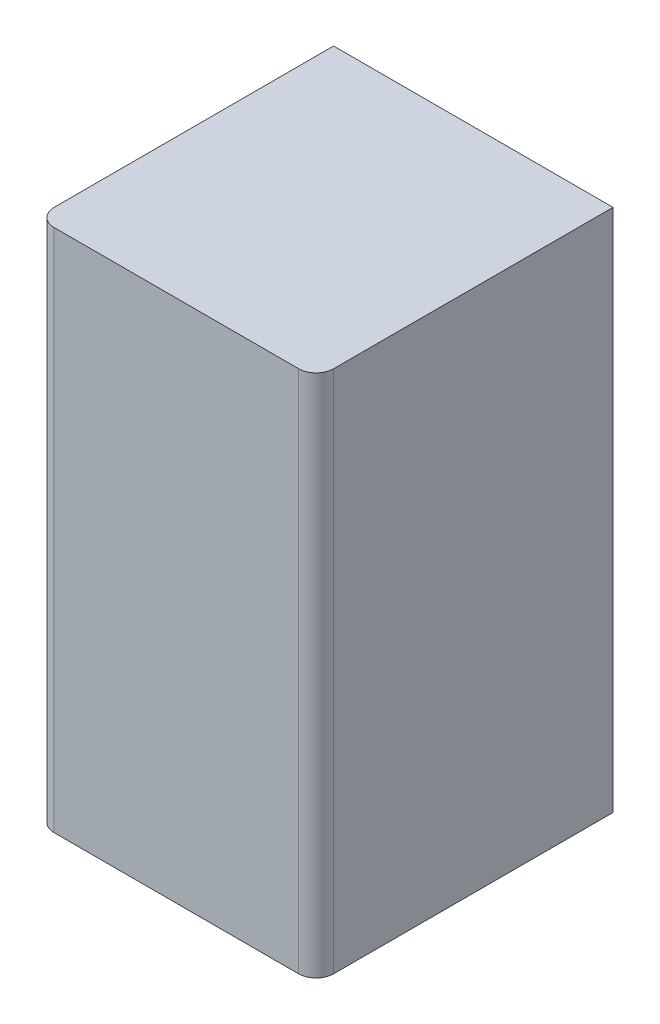
SolidWorks part; units mm, degrees
ref_plane "前视基准面" through (0, 0, 0) normal (0, 0, 1) x (1, 0, 0)
ref_plane "上视基准面" through (0, 0, 0) normal (0, 1, 0) x (1, 0, 0)
ref_plane "右视基准面" through (0, 0, 0) normal (1, 0, 0) x (0, 0, -1)
sketch "草图1" plane through (0, 0, 0) normal (0, 0, 1) x (1, 0, 0)
  line L0 (0, 48.626) -> (0, -83.7004) construction
  line L1 (-92.2698, 0) -> (95.8569, 0) construction
  line L2 (-8, 15) -> (8, 15)
  line L3 (-8, 15) -> (-8, -15)
  line L4 (-8, -15) -> (8, -15)
  line L5 (8, -15) -> (8, 15)
  dimension "D1" = 16
  dimension "D2" = 30
extrude "拉伸1" add sketch "草图1" along normal blind 0.1
sketch "草图2" plane through (0, 0, 0.1) normal (0, 0, 1) x (1, 0, 0)
  line L0 (0, 37.5456) -> (0, -35.199) construction
  line L1 (-34.3867, 0) -> (34.7477, 0) construction
  line L2 (-8, 15) -> (8, 15)
  line L3 (-8, 15) -> (-8, -15)
  line L4 (-8, -15) -> (8, -15)
  line L5 (8, -15) -> (8, 15)
  dimension "D1" = 16
  dimension "D2" = 30
extrude "拉伸2" add sketch "草图2" along normal blind 16.9
fillet "圆角1" radius 1 2 edges at (-8, 0, 17) (8, 0, 17)
